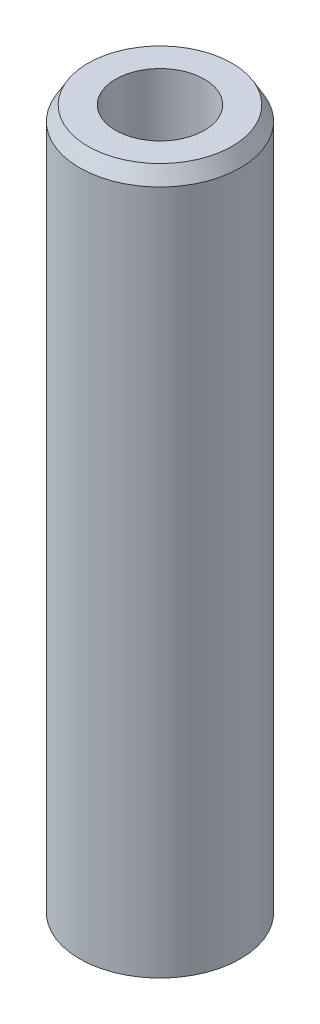
SolidWorks part; units mm, degrees
ref_plane "Front Plane" through (0, 0, 0) normal (0, 0, 1) x (1, 0, 0)
ref_plane "Top Plane" through (0, 0, 0) normal (0, 1, 0) x (1, 0, 0)
ref_plane "Right Plane" through (0, 0, 0) normal (1, 0, 0) x (0, 0, -1)
sketch "Sketch1" plane through (0, 0, 0) normal (0, 1, 0) x (1, 0, 0)
  circle A0 centre (0, 0) radius 12.5
  dimension "SHAFT_OD" = 25
extrude "Boss-Extrude1" add sketch "Sketch1" along normal blind 110.0787
sketch "Sketch2" plane through (0, 0, 0) normal (0, 1, 0) x (1, 0, 0)
  circle A0 centre (0, 0) radius 6.9
  dimension "BORE_D" = 13.7999
extrude "Cut-Extrude1" cut sketch "Sketch2" along normal through all
chamfer "Chamfer1" distance 2.2462 angle 30 2 edges at (0, 110.0787, 12.5) (0, 0, 12.5) first distance on face at (0, 110.0787, 12.5) first distance on face at (0, 0, 6.9)
